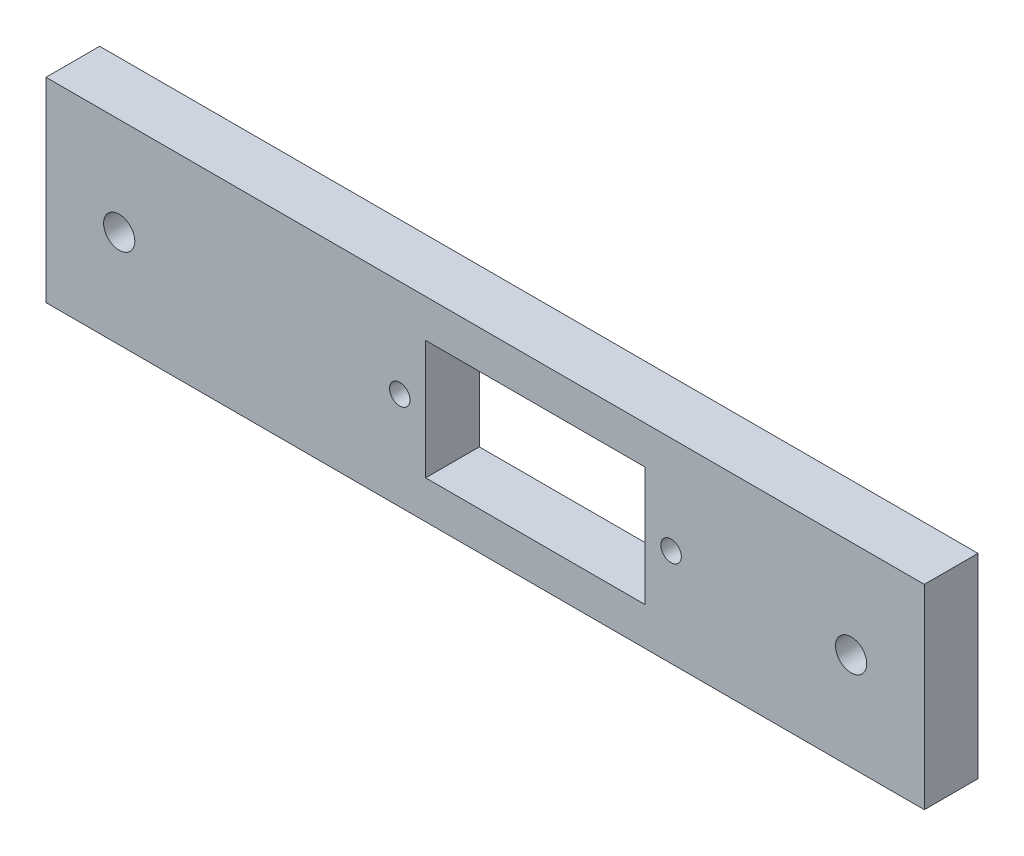
SolidWorks part; units mm, degrees
material "ﾁｰｸ材"
ref_plane "正面" through (0, 0, 0) normal (0, 0, 1) x (1, 0, 0)
ref_plane "平面" through (0, 0, 0) normal (0, 1, 0) x (1, 0, 0)
ref_plane "右側面" through (0, 0, 0) normal (1, 0, 0) x (0, 0, -1)
sketch "ｽｹｯﾁ1" plane through (0, 0, 0) normal (0, 0, 1) x (1, 0, 0)
  line L1 (-45, 10) -> (45, 10)
  line L2 (-45, 10) -> (-45, -10)
  line L3 (-45, -10) -> (45, -10)
  line L4 (45, 10) -> (45, -10)
  line L5 (-45, 10) -> (45, -10) construction
  line L6 (-45, -10) -> (45, 10) construction
  point P0 (0, 0)
  dimension "D1" = 20
  dimension "D2" = 90
extrude "ﾎﾞｽ - 押し出し1" add sketch "ｽｹｯﾁ1" along normal blind 5.5
sketch "ｽｹｯﾁ2" plane through (0, 0, 5.5) normal (0, 0, 1) x (1, 0, 0)
  line L0 (-45, 10) -> (-45, -10) construction
  line L1 (-6.1, 6.1) -> (16.4, 6.1)
  line L2 (-6.1, 6.1) -> (-6.1, -6.1)
  line L3 (-6.1, -6.1) -> (16.4, -6.1)
  line L4 (16.4, 6.1) -> (16.4, -6.1)
  line L5 (-6.1, 6.1) -> (16.4, -6.1) construction
  line L6 (-6.1, -6.1) -> (16.4, 6.1) construction
  line L7 (45, -10) -> (45, 10) construction
  circle A0 centre (-37.5, 0) radius 1.6
  circle A1 centre (37.5, 0) radius 1.6
  circle A2 centre (-8.75, 0) radius 1.05
  circle A3 centre (19.05, 0) radius 1.05
  point P0 (5.15, 0)
  dimension "D4" = 3.2
  dimension "D7" = 3.2
  dimension "D8" = 2.65
  dimension "D9" = 2.1
  dimension "D1" = 12.2
  dimension "D2" = 22.5
  dimension "D3" = 6.1
  dimension "D5" = 7.5
  dimension "D6" = 7.5
  dimension "D10" = 2.65
extrude "ｶｯﾄ - 押し出し1" cut sketch "ｽｹｯﾁ2" against normal through all
